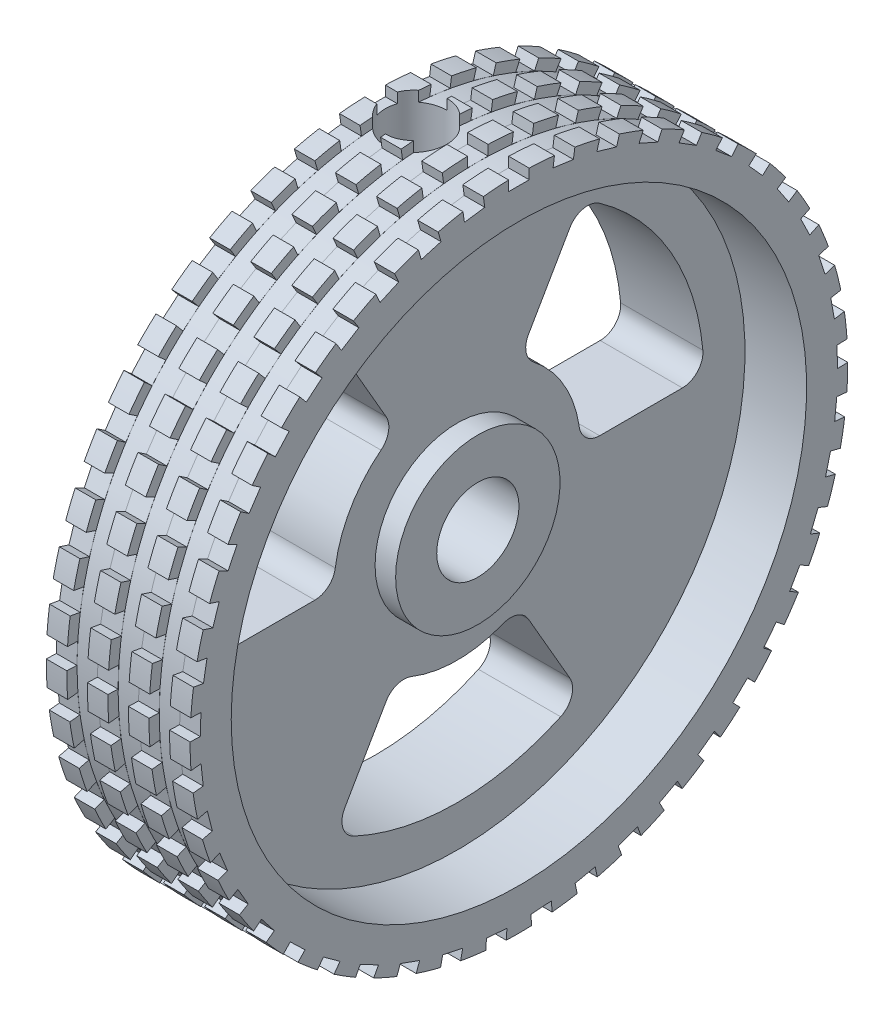
SolidWorks part; units mm, degrees
ref_plane "Front Plane" through (0, 0, 0) normal (0, 0, 1) x (1, 0, 0)
ref_plane "Top Plane" through (0, 0, 0) normal (0, 1, 0) x (1, 0, 0)
ref_plane "Right Plane" through (0, 0, 0) normal (1, 0, 0) x (0, 0, -1)
sketch "Sketch1" plane through (0, 0, 0) normal (0, 1, 0) x (1, 0, 0)
  line L0 (0, 0) -> (19.3216, 0) construction
  line L1 (0, 2) -> (0, 16)
  line L14 (0, 16) -> (7, 16)
  line L15 (7, 16) -> (7, 14)
  line L16 (7, 14) -> (4, 14)
  line L17 (4, 14) -> (4, 4)
  line L18 (4, 4) -> (5, 4)
  line L19 (5, 4) -> (5, 2)
  line L20 (5, 2) -> (0, 2)
  dimension "D1" = 7
  dimension "D2" = 4
  dimension "D3" = 5
  dimension "D4" = 8
  dimension "D5" = 4
  dimension "D6" = 28
  dimension "D7" = 32
revolve "Revolve1" add sketch "Sketch1" angle 360 about L0
sketch "Sketch3" plane through (0, 0, 0) normal (0, 0, 1) x (1, 0, 0)
  line L0 (0, 0) -> (7, 0) construction
  line L1 (7, -16) -> (7, 16) construction
  line L2 (2, 0) -> (2, 16)
  line L3 (2, 16) -> (3.5, 16)
  line L4 (3.5, 16) -> (3.5, 11.5)
  line L5 (3.5, 11.5) -> (2.9, 11.5)
  line L6 (2.9, 11.5) -> (2.9, 0)
  line L7 (2.9, 0) -> (2, 0)
  line L8 (0, 16) -> (0, -16) construction
  line L9 (7, 16) -> (0, 16) construction
  dimension "D1" = 4.5
  dimension "D2" = 1.5
  dimension "D3" = 2
  dimension "D4" = 0.9
revolve "Cut-Revolve1" cut sketch "Sketch3" angle 360 about L2
sketch "Sketch4" plane through (4, 0, 0) normal (1, 0, 0) x (0, 0, -1)
  line L2 (3, -5.1962) -> (6, -10.3923)
  line L3 (0, 0) -> (0, -12) construction
  line L4 (-3, -5.1962) -> (-6, -10.3923)
  arc A2 (-3, -5.1962) -> (3, -5.1962) centre (0, 0) ccw
  arc A3 (-6, -10.3923) -> (6, -10.3923) centre (0, 0) ccw
  point P1 (5.7786, -10.2629)
  point P6 (0, 0)
  point P8 (0, -6)
  point P12 (0, 0)
  point P14 (0, 0)
  dimension "D1" = 12
  dimension "D2" = 6
  dimension "D3" = 60
extrude "Cut-Extrude1" cut sketch "Sketch4" against normal blind 10
fillet "Fillet4" radius 1 4 edges at (2, -10.3923, -6) (2, -10.3923, 6) (2, -5.1962, -3) (2, -5.1962, 3)
pattern_circular "CirPattern1" count 3 over 360 about axis through (0, 0, 0) along (-1, 0, 0) of "Cut-Extrude1", "Fillet4"
sketch "Sketch5" plane through (0, 0, 0) normal (0, 1, 0) x (1, 0, 0)
  line L0 (7, 16) -> (0, 16) construction
  line L1 (5, 15.5) -> (6, 15.5)
  line L2 (5, 15.5) -> (5, 16)
  line L3 (5, 16) -> (6, 16)
  line L4 (6, 15.5) -> (6, 16)
  line L6 (7, -16) -> (7, 16) construction
  line L7 (0, 0) -> (7, 0) construction
  dimension "D1" = 1
  dimension "D2" = 0.5
  dimension "D3" = 1
revolve "Cut-Revolve2" cut sketch "Sketch5" angle 360 about L7
sketch "Sketch6" plane through (7, 0, 0) normal (1, 0, 0) x (0, 0, -1)
  line L0 (0, 0) -> (0, 16) construction
  line L14 (-0.5, 16) -> (0.5, 16)
  line L15 (-0.5, 16) -> (-0.5, 15.5)
  line L16 (-0.5, 15.5) -> (0.5, 15.5)
  line L17 (0.5, 16) -> (0.5, 15.5)
  circle A1 centre (0, 0) radius 16 construction
  point P9 (0, 16)
  circle M6 centre (0, 0) radius 16
  dimension "D1" = 1
  dimension "D2" = 0.5
extrude "Cut-Extrude5" cut sketch "Sketch6" against normal blind 10 contours L0 L16 L17 M6 | L16 L0 L15 M6
pattern_circular "CirPattern2" count 45 over 360 about axis through (0, 0, 0) along (-1, 0, 0) of "Cut-Extrude5"
pattern_linear "LPattern1" count 3 spacing 2 along (-1, 0, 0) of "Cut-Revolve2"
